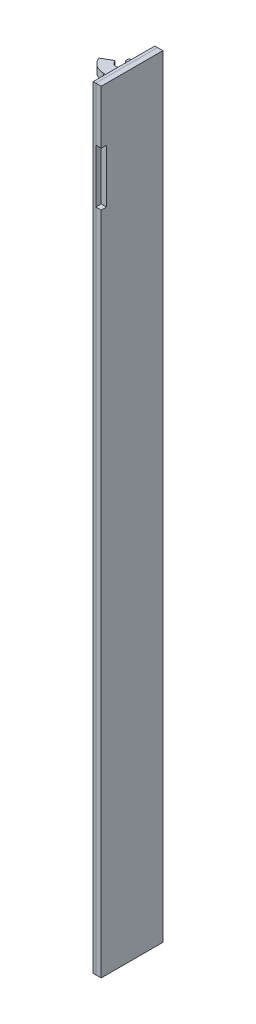
SolidWorks part; units mm, degrees
note: The reader was unsure of these and kept them because the rebuilt part matched: shared geometry of "Sketch1<2>", "Sketch3<2>", "Sketch4<2>".
ref_plane "Front Plane" through (0, 0, 0) normal (1, 0, 0) x (0, 1, 0)
ref_plane "Top Plane" through (0, 0, 0) normal (0, 0, 1) x (0, 1, 0)
ref_plane "Right Plane" through (0, 0, 0) normal (0, 1, 0) x (-1, 0, 0)
sketch "Sketch1" plane through (0, 0, 0) normal (1, 0, 0) x (0, 1, 0)
  line L1 (-144, 11.5) -> (144, 11.5)
  line L2 (-144, 11.5) -> (-144, -11.5)
  line L3 (-144, -11.5) -> (144, -11.5)
  line L4 (144, 11.5) -> (144, -11.5)
  line L5 (-144, 11.5) -> (144, -11.5) construction
  line L6 (-144, -11.5) -> (144, 11.5) construction
  point P0 (0, 0)
  dimension "D1" = 23
  dimension "D2" = 288
extrude "Boss-Extrude1" add sketch "Sketch1" along normal blind 1
extrude "Boss-Extrude5" add sketch "Sketch1<2>" along normal blind 2 from surface at 1 separate body starting at face at (1, 0, 0)
sketch "Sketch1<2>" plane through (0, 0, 0) normal (1, 0, 0) x (0, 1, 0) same geometry as "Sketch1"
sketch "Sketch2" plane through (0, 0, 0) normal (-1, 0, 0) x (0, -1, 0)
  line L1 (-136.65, 0.5) -> (-133.85, 0.5)
  line L2 (-136.65, 0.5) -> (-136.65, -11.5)
  line L3 (-136.65, -11.5) -> (-133.85, -11.5)
  line L4 (-133.85, 0.5) -> (-133.85, -11.5)
  line L5 (-135.25, 0.5) -> (-135.25, 11.5) construction
  line L6 (-144, 11.5) -> (144, 11.5) construction
  line L7 (-144, -11.5) -> (-144, 11.5) construction
  line L8 (144, -11.5) -> (-144, -11.5) construction
  line L9 (-133.85, 0.5) -> (-133.85, -11.5)
  line L10 (-136.65, 0.5) -> (-136.65, -11.5)
  line L11 (0, 2.2) -> (0, -2.2) construction
  line L12 (136.65, -11.5) -> (133.85, -11.5)
  line L13 (133.85, 0.5) -> (133.85, -11.5)
  line L14 (136.65, 0.5) -> (136.65, -11.5)
  line L15 (136.65, 0.5) -> (133.85, 0.5)
  line L16 (135.25, 0.5) -> (135.25, 11.5) construction
  line L17 (144, 11.5) -> (144, -11.5) construction
  dimension "D1" = 8.75
  dimension "D2" = 12
  dimension "D3" = 2.8
  dimension "D4" = 8.75
  dimension "D5" = 267.7
ref_plane "Plane1" through (0, 136.65, 0) normal (0, 1, 0) x (0, 0, -1)
sketch "Sketch3" plane through (0, 136.65, 0) normal (0, 1, 0) x (0, 0, -1)
  line L2 (-0.5, 0) -> (11.5, 0) construction
  line L4 (6.75, 8.05) -> (5.875, 9.5655) construction
  line L5 (6.75, 8.05) -> (8.5, 8.05) construction
  line L7 (11.5, -1) -> (11.5, 0) construction
  line L8 (11.5, 0) -> (-11.5, 0) construction
  line L12 (8.7343, 8.05) -> (9.75, 8.05)
  line L13 (0.5, 8.05) -> (0.5, 7.84)
  line L14 (11.5, 0) -> (-11.5, 0) construction
  line L15 (10, 7.8) -> (10, 1.7071)
  line L16 (10.1464, 1.3536) -> (11.5, 0)
  line L17 (6.616, 10.2821) -> (4.616, 13.7462)
  line L18 (0.5, 0) -> (11.5, 0)
  line L19 (0.36, 7.7) -> (0.14, 7.7)
  line L20 (0, 7.56) -> (0, 4.84)
  line L21 (0.14, 4.7) -> (0.36, 4.7)
  line L22 (0.5, 4.56) -> (0.5, 0)
  line L23 (3.625, 13.4627) -> (4.2745, 13.8377)
  line L24 (5.875, 9.5655) -> (6.5245, 9.9405)
  arc A0 (8.4863, 7.8313) -> (5.875, 9.5655) centre (6.75, 8.05) cw
  arc A4 (0.5, 8.05) -> (3.625, 13.4627) centre (6.75, 8.05) cw
  arc A6 (9.75, 8.05) -> (10, 7.8) centre (9.75, 7.8) cw
  arc A7 (10, 1.7071) -> (10.1464, 1.3536) centre (10.5, 1.7071) ccw
  arc A9 (8.4863, 7.8313) -> (8.7343, 8.05) centre (8.7343, 7.8) cw
  arc A10 (0.36, 4.7) -> (0.5, 4.56) centre (0.36, 4.56) cw
  arc A11 (0.36, 7.7) -> (0.5, 7.84) centre (0.36, 7.84) ccw
  arc A12 (0, 4.84) -> (0.14, 4.7) centre (0.14, 4.84) ccw
  arc A13 (0.14, 7.7) -> (0, 7.56) centre (0.14, 7.56) ccw
  arc A14 (6.5245, 9.9405) -> (6.616, 10.2821) centre (6.3995, 10.1571) ccw
  arc A15 (4.2745, 13.8377) -> (4.616, 13.7462) centre (4.3995, 13.6212) cw
  point P0 (11.5, 0)
  point P1 (5.1972, 10.1668)
  point P2 (0, 0)
  point P3 (0, 0)
  point P11 (0, 0)
  point P22 (3.2487, 13.0558)
  point P26 (10, 8.05)
  point P30 (4.6791, 9.5102)
  point P41 (0.5, 4.7)
  point P44 (0.5, 7.7)
  point P47 (0, 4.7)
  point P50 (0, 7.7)
  point P51 (0, 0)
  point P53 (0, 0)
  point P58 (4.491, 13.9627)
  point P59 (0, 0)
  point P60 (0, 0)
  point P61 (4.6, 9.5376)
  point P62 (0, 0)
  dimension "D1" = 3
  dimension "D2" = 6.3
  dimension "D3" = 1.75
  dimension "D4" = 120
  dimension "D6" = 11
  dimension "D8" = 45
  dimension "D9" = 1.5
  dimension "D10" = 1
  dimension "D11" = 0.25
  dimension "D12" = 0.5
  dimension "D15" = 0.14
  dimension "D16" = 0.5
  dimension "D5" = 1.75
  dimension "D13" = 3
  dimension "D14" = 4.7
extrude "Boss-Extrude2" add sketch "Sketch3" against normal up to vertex (2.8 mm away) up to point (0, 133.85, -11.5)
extrude "Boss-Extrude3" add sketch "Sketch3<2>" against normal up to vertex (273.3 mm away) from vertex at -270.5 starting at point (0, -133.85, -11.5)
sketch "Sketch3<2>" plane through (0, 136.65, 0) normal (0, 1, 0) x (0, 0, -1) same geometry as "Sketch3"
sketch "Sketch4" plane through (3, 0, 0) normal (1, 0, 0) x (0, 1, 0)
  line L6 (105.8946, 6.8232) -> (108.3946, 4.3232)
  line L7 (108.3946, 4.3232) -> (110.8946, 6.8232)
  line L8 (110.8946, 6.8232) -> (105.8946, 6.8232)
  line L13 (-30, -5) -> (-29, -5)
  line L14 (-29, -5) -> (-29, -0.5)
  line L15 (-29, -0.5) -> (-10, -0.5)
  line L16 (-10, -0.5) -> (-10, 5)
  line L17 (-10, 5) -> (-30, 5)
  line L19 (-30, 0.5) -> (-11, 0.5)
  line L20 (-11, 0.5) -> (-11, 4)
  line L21 (-11, 4) -> (-30, 4)
  line L22 (10, 5) -> (10, 4)
  line L23 (10, 4) -> (0.5, 4)
  line L24 (0.5, 4) -> (0.5, -5)
  line L27 (0.5, -5) -> (-10, -5)
  line L28 (10, 5) -> (-0.5, 5)
  line L29 (-0.5, 5) -> (-0.5, -4)
  line L32 (-0.5, -4) -> (-10, -4)
  line L33 (-10, -4) -> (-10, -5)
  line L34 (29.9456, 5) -> (32, 5)
  line L35 (32, 5) -> (23.0272, 0)
  line L36 (23.0272, 0) -> (32, -5)
  line L37 (32, -5) -> (29.9456, -5)
  line L38 (29.9456, -5) -> (22, -0.5724)
  line L39 (22, -0.5724) -> (14.0544, -5)
  line L40 (14.0544, -5) -> (12, -5)
  line L41 (12, -5) -> (20.9728, 0)
  line L42 (20.9728, 0) -> (12, 5)
  line L43 (12, 5) -> (14.0544, 5)
  line L44 (14.0544, 5) -> (22, 0.5724)
  line L45 (22, 0.5724) -> (29.9456, 5)
  line L46 (32, 5) -> (12, 5) construction
  line L47 (10, 5) -> (-10, 5) construction
  line L48 (0.5, -5) -> (-0.5, -4) construction
  line L49 (22, -0.5724) -> (22, 0.5724) construction
  line L50 (23.0272, 0) -> (20.9728, 0) construction
  line L51 (0.5, 4) -> (-0.5, 5) construction
  line L52 (12, 5) -> (12, -5) construction
  line L53 (32, 5) -> (32, -5) construction
  line L54 (-30, 5) -> (-30, 4)
  line L55 (-30, 0.5) -> (-30, -5)
  line L56 (-11, 0.5) -> (-10, -0.5) construction
  line L57 (-11, 4) -> (-10, 5) construction
  line L58 (-30, 0.5) -> (-29, -0.5) construction
  line L59 (-10, 5) -> (-10, -5) construction
  line L60 (-30, -5) -> (-10, -5) construction
  line L61 (-10, -5) -> (-10, 5) construction
  line L62 (-30, 0) -> (-10, 0) construction
  line L63 (-10, 0) -> (10, 0) construction
  line L64 (14.0544, -5) -> (13.5676, -4.1265) construction
  line L66 (12, 5) -> (10, 5) construction
  text T0 "OPEN" font "Arial" height 2.5
  point P29 (-10.5, 0)
  dimension "D2" = 2
  dimension "D4" = 2.5
  dimension "D5" = 4
  dimension "D6" = 1
  dimension "D7" = 1
  dimension "D9" = 10
  dimension "D10" = 20
extrude "Cut-Extrude1" cut sketch "Sketch4" along normal blind 1 from vertex at -2 starting at point (1, 144, 11.5)
extrude "Boss-Extrude4" add sketch "Sketch4<2>" along normal blind 1 from vertex at -2 separate body
sketch "Sketch4<2>" plane through (3, 0, 0) normal (1, 0, 0) x (0, 1, 0) same geometry as "Sketch4"
sketch "Sketch6" plane through (3, 0, 0) normal (1, 0, 0) x (0, 1, 0)
  line L0 (-144, 11.5) -> (144, 11.5) construction
  line L1 (124, 11.5) -> (104, 11.5)
  line L2 (124, 11.5) -> (124, 9.5)
  line L3 (124, 9.5) -> (104, 9.5)
  line L4 (104, 11.5) -> (104, 9.5)
  line L5 (144, 11.5) -> (144, -11.5) construction
  dimension "D1" = 20
  dimension "D2" = 20
  dimension "D3" = 2
extrude "Cut-Extrude2" cut sketch "Sketch6" against normal blind 2
